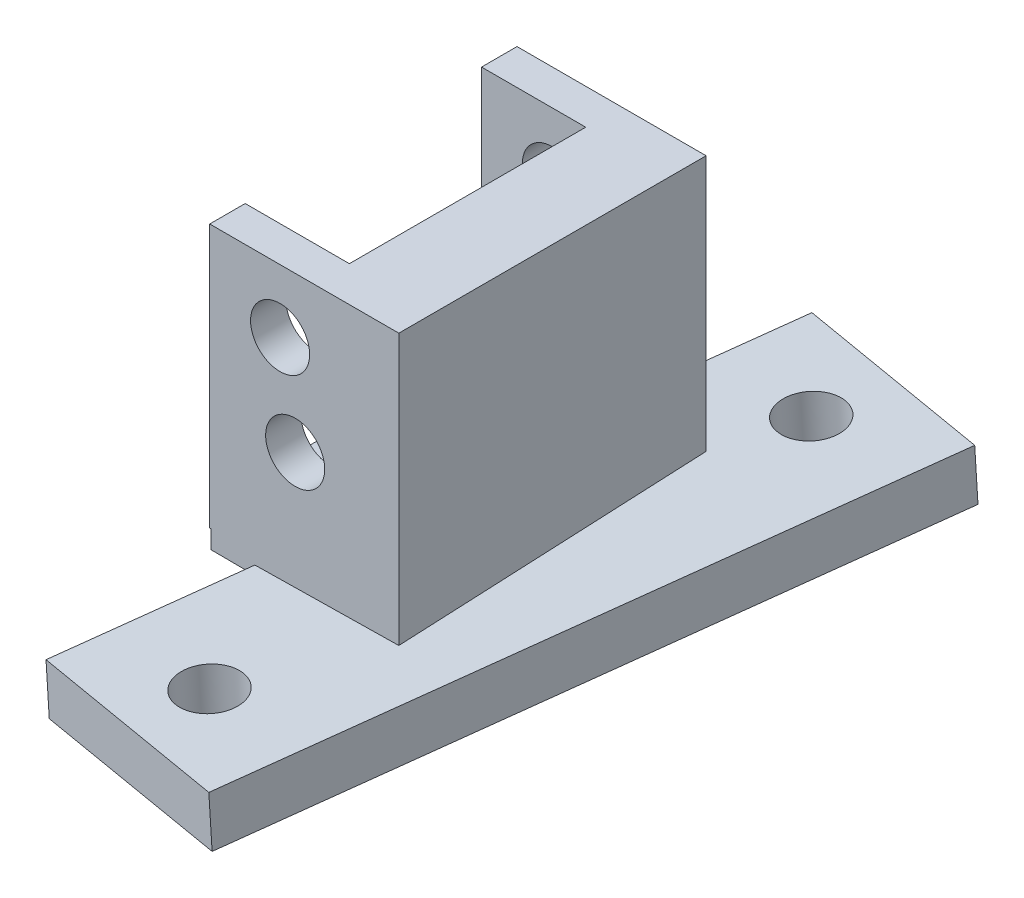
SolidWorks part; units mm, degrees
ref_plane "Front Plane" through (0, 0, 0) normal (0, 0, 1) x (1, 0, 0)
ref_plane "Top Plane" through (0, 0, 0) normal (0, 1, 0) x (1, 0, 0)
ref_plane "Right Plane" through (0, 0, 0) normal (1, 0, 0) x (0, 0, -1)
sketch "Sketch1" plane through (0, 0, 0) normal (0, 0, 1) x (1, 0, 0)
  line L0 (427.4923, 249.3739) -> (458.8626, 254.5214) construction
  line L1 (448.4353, 278.7761) -> (468.7553, 278.7761)
  line L2 (448.4353, 278.7761) -> (448.4353, 250.4861)
  line L3 (448.4353, 250.4861) -> (468.7553, 250.4861)
  line L4 (468.7553, 278.7761) -> (468.7553, 250.4861)
  line L5 (427.4923, 249.3739) -> (458.8626, 254.5214)
  line L6 (448.4353, 252.8104) -> (458.8626, 254.5214)
  arc A0 (461.3669, 277.5061) -> (454.7498, 279.5862) centre (455.9966, 271.9877) ccw construction
  arc A1 (463.4772, 270.1621) -> (461.3669, 277.5061) centre (455.9966, 271.9877) ccw construction
  arc A2 (463.4772, 270.1621) -> (464.1208, 266.2396) centre (468.4124, 268.9577) ccw construction
  arc A3 (464.4679, 258.6072) -> (464.1208, 266.2396) centre (457.6159, 262.1197) ccw construction
  arc A4 (458.8626, 254.5214) -> (464.4679, 258.6072) centre (457.6159, 262.1197) ccw construction
  arc A5 (461.3669, 277.5061) -> (454.7498, 279.5862) centre (455.9966, 271.9877) ccw
  arc A6 (463.4772, 270.1621) -> (461.3669, 277.5061) centre (455.9966, 271.9877) ccw
  arc A7 (463.4772, 270.1621) -> (464.1208, 266.2396) centre (468.4124, 268.9577) ccw
  arc A8 (464.4679, 258.6072) -> (464.1208, 266.2396) centre (457.6159, 262.1197) ccw
  arc A9 (458.8626, 254.5214) -> (464.4679, 258.6072) centre (457.6159, 262.1197) ccw
  arc A10 (458.8626, 254.5214) -> (464.4679, 258.6072) centre (457.6159, 262.1197) ccw
  arc A11 (464.4679, 258.6072) -> (464.1208, 266.2396) centre (457.6159, 262.1197) ccw
  arc A12 (464.1208, 266.2396) -> (463.4772, 270.1621) centre (468.4124, 268.9577) cw
  arc A13 (463.4772, 270.1621) -> (461.3669, 277.5061) centre (455.9966, 271.9877) ccw
  arc A14 (461.3669, 277.5061) -> (459.6312, 278.7761) centre (455.9966, 271.9877) ccw
  circle A15 centre (457.6159, 262.1197) radius 3.175
  circle A16 centre (455.9966, 271.9877) radius 3.175
  dimension "D1" = 4.0353
  dimension "D2" = 1.27
  dimension "D3" = 20.32
  dimension "D4" = 10.16
extrude "Boss-Extrude1" add sketch "Sketch1" against normal blind 29.21 contours A9 L5 L2 L3 L4 L1 A5 A6 A7 A8 region at (464.1933, 278.4278, 0)
sketch "Sketch2" plane through (0, 0, 0) normal (0, 0, 1) x (1, 0, 0)
  line L0 (448.4353, 252.8104) -> (448.4353, 278.7761)
  line L1 (448.4353, 278.7761) -> (468.7553, 278.7761)
  line L2 (468.7553, 278.7761) -> (468.7553, 250.4861)
  line L3 (468.7553, 250.4861) -> (448.4353, 250.4861)
  line L4 (448.4353, 250.4861) -> (448.4353, 252.8104)
  circle A0 centre (455.9966, 271.9877) radius 3.175
  circle A1 centre (457.6159, 262.1197) radius 3.175
  dimension "D1" = 6.35
  dimension "D2" = 6.35
extrude "Boss-Extrude2" add sketch "Sketch2" along normal blind 3.81
sketch "Sketch3" plane through (0, 0, -25.4) normal (0, 0, -1) x (-1, 0, 0)
  line L0 (-448.4353, 252.8104) -> (-458.8626, 254.5214) construction
  line L1 (-448.4353, 252.8104) -> (-458.8626, 254.5214)
  line L2 (-448.4353, 252.8104) -> (-448.4353, 278.7761)
  line L3 (-448.4353, 278.7761) -> (-459.6312, 278.7761)
  line L4 (-458.8626, 254.5214) -> (-448.4353, 252.8104)
  arc A0 (-464.1208, 266.2396) -> (-458.8626, 254.5214) centre (-457.6159, 262.1197) ccw construction
  arc A1 (-464.1208, 266.2396) -> (-463.4772, 270.1621) centre (-468.4124, 268.9577) ccw construction
  arc A2 (-459.6312, 278.7761) -> (-463.4772, 270.1621) centre (-455.9966, 271.9877) ccw construction
  arc A3 (-464.1208, 266.2396) -> (-458.8626, 254.5214) centre (-457.6159, 262.1197) ccw
  arc A4 (-464.1208, 266.2396) -> (-463.4772, 270.1621) centre (-468.4124, 268.9577) ccw
  arc A5 (-459.6312, 278.7761) -> (-463.4772, 270.1621) centre (-455.9966, 271.9877) ccw
  arc A6 (-459.6312, 278.7761) -> (-463.4772, 270.1621) centre (-455.9966, 271.9877) ccw
  arc A7 (-463.4772, 270.1621) -> (-464.1208, 266.2396) centre (-468.4124, 268.9577) cw
  arc A8 (-464.1208, 266.2396) -> (-458.8626, 254.5214) centre (-457.6159, 262.1197) ccw
  circle A9 centre (-457.6159, 262.1197) radius 3.175
  circle A10 centre (-455.9966, 271.9877) radius 3.175
  line M4 (-423.8853, 271.3557) -> (-461.3669, 277.5061)
  arc M5 (-461.3669, 277.5061) -> (-463.4772, 270.1621) centre (-455.9966, 271.9877) ccw
  arc M6 (-463.4772, 270.1621) -> (-464.1208, 266.2396) centre (-468.4124, 268.9577) cw
  arc M7 (-464.1208, 266.2396) -> (-464.4679, 258.6072) centre (-457.6159, 262.1197) ccw
  line M8 (-464.4679, 258.6072) -> (-424.8406, 252.1047)
  circle M9 centre (-457.6159, 262.1197) radius 3.175
  circle M10 centre (-455.9966, 271.9877) radius 3.175
  dimension "D1" = 6.35
  dimension "D2" = 6.35
extrude "Boss-Extrude3" add sketch "Sketch3" along normal up to surface (3.81 mm away) contours L2 M8 M4 M5 M6 M7 M9 M10 | A3 L1 L2 M8 | L3 A5 L2 M4 region at (455.7154, 255.665, -25.4) region at (456.0581, 266.5213, -25.4) region at (453.6849, 277.5014, -25.4) up to face at (460.587, 262.6797, -29.21)
ref_plane "Plane1" through (-3.842, 241.8411, 11.4068) normal (-0.0159, 0.9988, 0.0471) x (0.9999, 0.0158, 0.0007)
sketch "Sketch4" plane through (-3.842, 241.8411, 11.4068) normal (-0.0159, 0.9988, 0.0471) x (0.9999, 0.0158, 0.0007)
  line L0 (453.8175, -11.1538) -> (466.1674, 58.8857)
  line L1 (466.1674, 58.8857) -> (487.4294, 55.1367)
  line L2 (487.4294, 55.1367) -> (475.0795, -14.9028)
  line L3 (475.0795, -14.9028) -> (453.8175, -11.1538)
  line L4 (452.3517, 7.9956) -> (472.6692, 7.9956) construction
  circle A0 centre (465.7717, -5.5241) radius 3.175
  circle A1 centre (475.4752, 49.507) radius 3.175
  dimension "D6" = 7.62
  dimension "D8" = 6.35
  dimension "D10" = 6.35
  dimension "D1" = 100
  dimension "D2" = 16.51
  dimension "D3" = 71.12
  dimension "D4" = 6.35
  dimension "D5" = 21.59
  dimension "D7" = 10.795
  dimension "D9" = 7.62
  dimension "D11" = 10.795
extrude "Boss-Extrude4" add sketch "Sketch4" against normal blind 5.588
sketch "Sketch5" plane through (0, 0, 3.81) normal (0, 0, 1) x (1, 0, 0)
  line L0 (468.7553, 250.4861) -> (448.5605, 250.4861)
  line L1 (448.4353, 250.4861) -> (468.7553, 250.4861) construction
  line L2 (448.5605, 250.4861) -> (448.5605, 248.529)
  line L3 (448.5605, 248.529) -> (468.7553, 248.3932)
  line L4 (468.7553, 248.3932) -> (468.7553, 250.4861)
extrude "Boss-Extrude5" add sketch "Sketch5" against normal up to surface (33.02 mm away) up to face at (458.7693, 260.1501, -29.21)
